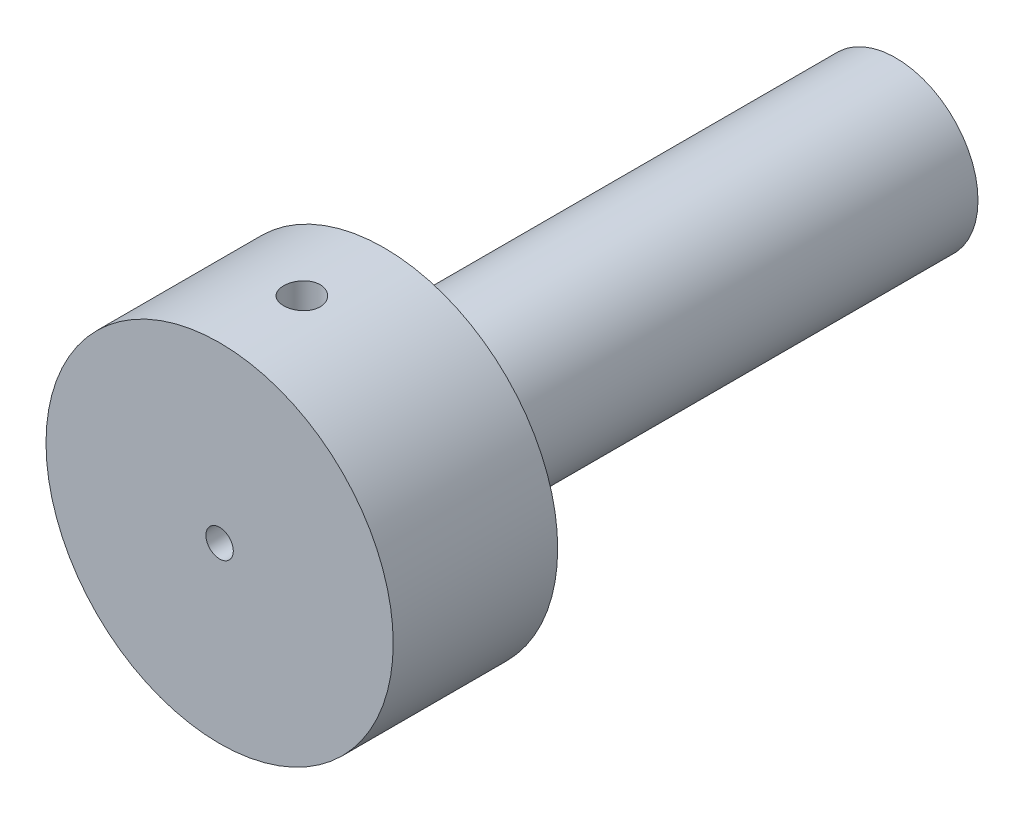
SolidWorks part; units mm, degrees
ref_plane "Płaszczyzna przednia" through (0, 0, 0) normal (0, 0, 1) x (1, 0, 0)
ref_plane "Płaszczyzna górna" through (0, 0, 0) normal (0, 1, 0) x (1, 0, 0)
ref_plane "Płaszczyzna prawa" through (0, 0, 0) normal (1, 0, 0) x (0, 0, -1)
ref_plane "Płaszczyzna1" through (0, -15, 0) normal (0, 1, 0) x (1, 0, 0)
sketch "Szkic1" plane through (0, -15, 0) normal (0, 1, 0) x (1, 0, 0)
  line L0 (0, -56) -> (2, -56)
  line L1 (2, -56) -> (2, -62)
  line L2 (2, -62) -> (0, -63.1547)
  line L3 (0, -63.1547) -> (0, -56)
  line L4 (0, -63.1547) -> (0, -56) construction
sketch "Szkic2" plane through (0, 0, 0) normal (1, 0, 0) x (0, 0, -1)
  line L0 (-56, 0) -> (-56, 9)
  line L1 (-56, 9) -> (0, 9)
  line L2 (0, 9) -> (0, 0)
  line L3 (0, 0) -> (-56, 0)
  line L4 (0, 0) -> (-56, 0) construction
sketch "Szkic3" plane through (0, 0, 0) normal (1, 0, 0) x (0, 0, -1)
  line L0 (-74, 0) -> (-74, 19)
  line L1 (-74, 19) -> (-56, 19)
  line L2 (-56, 19) -> (-56, 0)
  line L3 (-56, 0) -> (-74, 0)
  line L4 (-56, 0) -> (-74, 0) construction
sketch "Szkic4" plane through (0, 0, 0) normal (1, 0, 0) x (0, 0, -1)
  line L0 (-74, 0) -> (-74, 1.5)
  line L1 (-74, 1.5) -> (0, 2.7917)
  line L2 (0, 2.7917) -> (0, 0)
  line L3 (0, 0) -> (-74, 0)
  line L4 (0, 0) -> (-74, 0) construction
sketch "Szkic5" plane through (0, 0, 0) normal (1, 0, 0) x (0, 0, -1)
  line L0 (-65, 11.8453) -> (-67, 13)
  line L1 (-67, 13) -> (-67, 19)
  line L2 (-67, 19) -> (-65, 19)
  line L3 (-65, 19) -> (-65, 11.8453)
  line L4 (-65, 19) -> (-65, 11.8453) construction
sketch "Szkic6" plane through (0, 0, 0) normal (1, 0, 0) x (0, 0, -1)
  line L0 (-56, 9) -> (-53, 9)
  line L1 (-56, 12) -> (-56, 9)
  line L2 (0, 0) -> (-56, 0) construction
  arc A0 (-53, 9) -> (-56, 12) centre (-53, 12) cw
revolve "Obrót1" add sketch "Szkic2" angle 360 about L4 reverse direction yes
revolve "Obrót2" add sketch "Szkic3" angle 360 about L4 reverse direction yes
revolve "Wycięcie-obrót1" cut sketch "Szkic4" angle 360 about L4 reverse direction yes
revolve "Wycięcie-obrót2" cut sketch "Szkic5" angle 360 about L4 reverse direction yes
revolve "Obrót3" add sketch "Szkic6" angle 360 about L2 reverse direction yes
revolve "Wycięcie-obrót3" cut sketch "Szkic1" angle 360 about L4 other way angle 360 reverse direction yes
ref_plane "Płaszczyzna2" through (0, 0, 74) normal (0, 0, 1) x (1, 0, 0)
ref_plane "IP1 XY" through (0, 0, 74) normal (0, 0, 1) x (1, 0, 0)
ref_plane "IP1 XZ" through (0, 0, 0) normal (0, -1, 0) x (-1, 0, 0)
ref_plane "IP1 YZ" through (0, 0, 0) normal (1, 0, 0) x (0, 0, -1)
ref_axis "IP1 X" through (-80.9, 0, 74) along (1, 0, 0)
ref_axis "IP1 Y" through (0, -50, 74) along (0, 1, 0)
ref_axis "IP1 Z" through (0, 0, 80.9) along (0, 0, -1)
sketch3d "IP1"
  point P0 (0, 0, 74)
